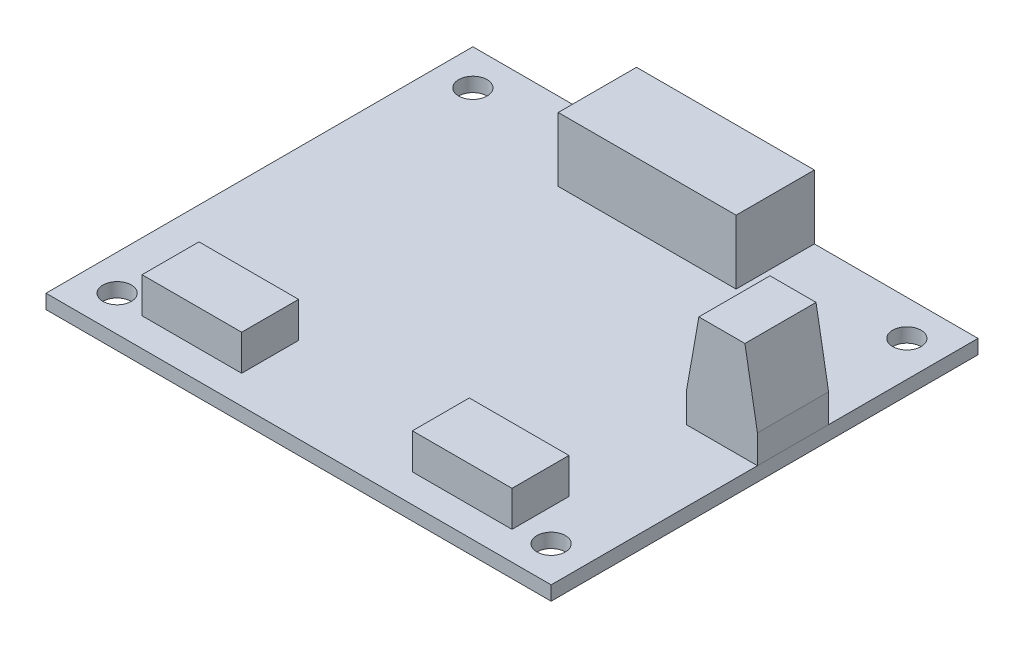
SolidWorks part; units mm, degrees
ref_plane "Front Plane" through (0, 0, 0) normal (0, 0, 1) x (1, 0, 0)
ref_plane "Top Plane" through (0, 0, 0) normal (0, 1, 0) x (1, 0, 0)
ref_plane "Right Plane" through (0, 0, 0) normal (1, 0, 0) x (0, 0, -1)
sketch "Sketch1" plane through (0, 0, 0) normal (0, 1, 0) x (1, 0, 0)
  line L1 (0, 0) -> (71, 0)
  line L2 (0, 0) -> (0, 60)
  line L3 (0, 60) -> (71, 60)
  line L4 (71, 0) -> (71, 60)
  dimension "D1" = 71
  dimension "D2" = 60
extrude "Boss-Extrude1" add sketch "Sketch1" along normal blind 2
sketch "Sketch2" plane through (0, 2, 0) normal (0, 1, 0) x (1, 0, 0)
  line L0 (35.5, 60) -> (35.5, 0) construction
  line L1 (71, 60) -> (0, 60) construction
  line L2 (0, 0) -> (71, 0) construction
  line L3 (0, 30) -> (71, 30) construction
  line L4 (0, 60) -> (0, 0) construction
  line L5 (71, 0) -> (71, 60) construction
  line L6 (47.5, 12) -> (47.5, 4)
  line L7 (71, 39) -> (61, 39)
  line L8 (71, 39) -> (71, 29)
  line L9 (71, 29) -> (61, 29)
  line L10 (61, 39) -> (61, 29)
  line L11 (23, 60) -> (48, 60)
  line L12 (23, 60) -> (23, 49)
  line L13 (23, 49) -> (48, 49)
  line L14 (48, 60) -> (48, 49)
  line L15 (9.5, 12) -> (23.5, 12)
  line L16 (9.5, 12) -> (9.5, 4)
  line L17 (9.5, 4) -> (23.5, 4)
  line L18 (23.5, 12) -> (23.5, 4)
  line L19 (61.5, 4) -> (47.5, 4)
  line L20 (61.5, 12) -> (61.5, 4)
  line L21 (61.5, 12) -> (47.5, 12)
  circle A0 centre (66, 55) radius 2
  circle A1 centre (5, 55) radius 2
  circle A2 centre (66, 5) radius 2
  circle A3 centre (5, 5) radius 2
  point P29 (35.5, 60)
  line M10 (71, 0) -> (71, 60)
  line M11 (71, 60) -> (0, 60)
  dimension "D1" = 4
  dimension "D2" = 5
  dimension "D3" = 5
  dimension "D4" = 10
  dimension "D5" = 21
  dimension "D6" = 10
  dimension "D7" = 25
  dimension "D8" = 11
  dimension "D9" = 8
  dimension "D10" = 14
  dimension "D11" = 4.5
  dimension "D12" = 4
extrude "Boss-Extrude2" add sketch "Sketch2" along normal blind 9 separate body contours L14 L12 L13 M11 region at (35.5, 2, -54.5)
extrude "Boss-Extrude3" add sketch "Sketch2<3>" along normal blind 14 separate body contours L7 L10 L9 M10 region at (66, 2, -34)
sketch "Sketch2<3>" plane through (0, 2, 0) normal (0, 1, 0) x (1, 0, 0) same geometry as "Sketch2"
chamfer "Chamfer1" distance 10 angle 10 2 edges at (61, 16, -34) (71, 16, -34) first distance on face at (61, 9, -34) first distance on face at (71, 9, -34)
extrude "Cut-Extrude2" cut sketch "Sketch2<5>" against normal up to next (2 mm away) contours A1 | A3 | A2 | A0 region at (66, 2, -55) region at (5, 2, -55) region at (66, 2, -5) region at (5, 2, -5)
sketch "Sketch2<5>" plane through (0, 2, 0) normal (0, 1, 0) x (1, 0, 0) same geometry as "Sketch2"
extrude "Boss-Extrude4" add sketch "Sketch2<6>" along normal blind 5 contours L18 L15 L16 L17 | L20 L21 L6 L19 region at (54.5, 2, -8) region at (16.5, 2, -8)
sketch "Sketch2<6>" plane through (0, 2, 0) normal (0, 1, 0) x (1, 0, 0) same geometry as "Sketch2"
